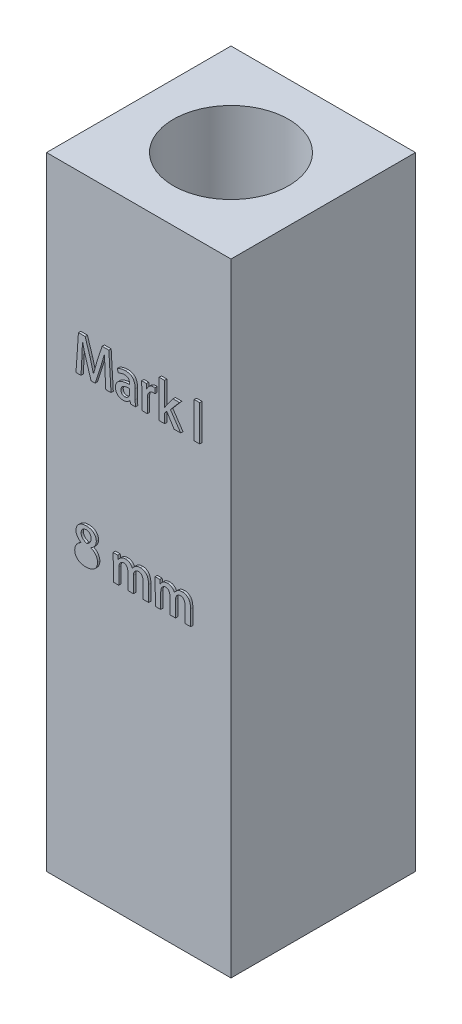
SolidWorks part; units mm, degrees
note: The reader was unsure of these and kept them because the rebuilt part matched: shared geometry of "Croquis2<2>".
ref_plane "Alzado" through (0, 0, 0) normal (0, 0, 1) x (1, 0, 0)
ref_plane "Planta" through (0, 0, 0) normal (0, 1, 0) x (1, 0, 0)
ref_plane "Vista lateral" through (0, 0, 0) normal (1, 0, 0) x (0, 0, -1)
sketch "Croquis1" plane through (0, 0, 0) normal (0, 1, 0) x (1, 0, 0)
  line L1 (-4, 4) -> (4, 4)
  line L2 (-4, 4) -> (-4, -4)
  line L3 (-4, -4) -> (4, -4)
  line L4 (4, 4) -> (4, -4)
  line L5 (-4, 4) -> (4, -4) construction
  line L6 (-4, -4) -> (4, 4) construction
  circle A0 centre (0, 0) radius 2.5
  point P0 (0, 0)
  dimension "D1" = 5
  dimension "D2" = 8
extrude "Saliente-Extruir1" add sketch "Croquis1" along normal blind 27
sketch "Croquis2" plane through (0, 0, 4) normal (0, 0, 1) x (1, 0, 0)
  text T0 "Mark I\r\n \r\n8 mm" font "@Adobe Heiti Std R" height in points 5
split line "Línea de partición1"
extrude "Saliente-Extruir2" add sketch "Croquis2<2>" along normal blind 0.1
sketch "Croquis2<2>" plane through (0, 0, 4) normal (0, 0, 1) x (1, 0, 0) same geometry as "Croquis2"
